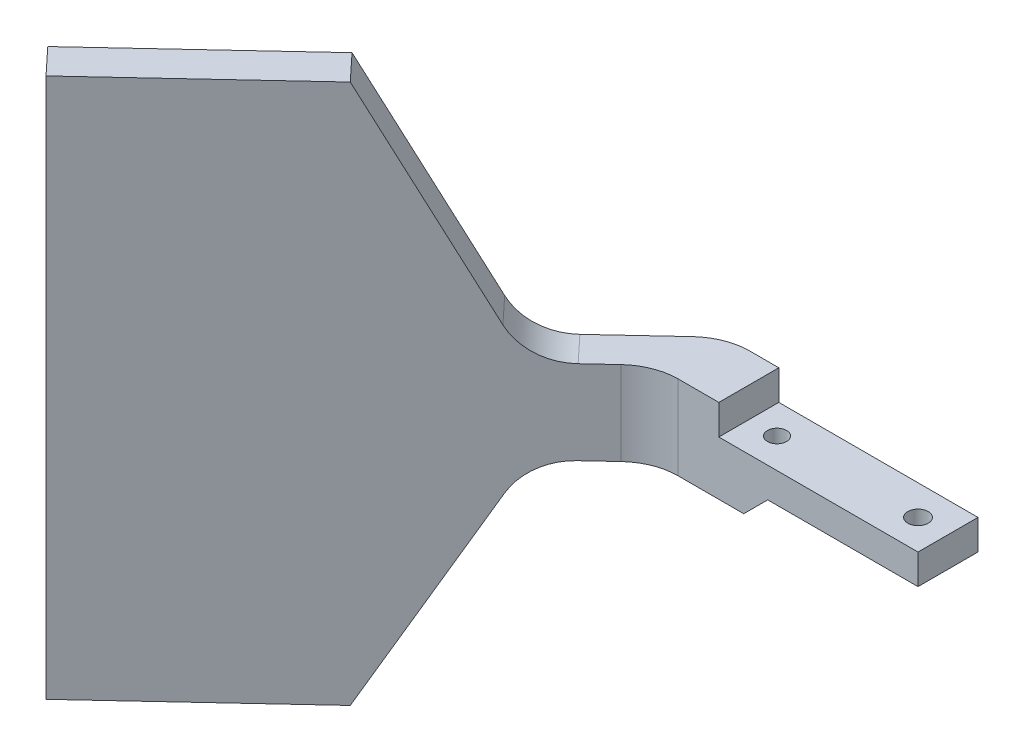
SolidWorks part; units mm, degrees
ref_plane "Front" through (0, 0, 0) normal (0, 0, 1) x (1, 0, 0)
ref_plane "Top" through (0, 0, 0) normal (0, 1, 0) x (1, 0, 0)
ref_plane "Right" through (0, 0, 0) normal (1, 0, 0) x (0, 0, -1)
sketch "Sketch1" plane through (0, 0, 0) normal (0, 1, 0) x (1, 0, 0)
  line L0 (0, 10) -> (0, 0)
  line L1 (0, 0) -> (42, 0)
  line L3 (0, 10) -> (42, 10)
  line L4 (42, 0) -> (42, 10)
  line L9 (0, 10) -> (-58.5083, -44.5599)
  line L10 (-58.5083, -44.5599) -> (-54.4163, -48.948)
  line L11 (0, 10) -> (4.092, 5.6119)
  line L12 (-54.4163, -48.948) -> (4.092, 5.6119)
  line L13 (0, 0) -> (-1.926, 0)
  line L14 (-1.926, 0) -> (0, 1.796)
  line L15 (0, 1.796) -> (0, 0)
  dimension "D1" = 10
  dimension "D2" = 42
  dimension "D3" = 223
  dimension "D4" = 80
  dimension "D5" = 6
  dimension "D6" = 270
extrude "Boss-Extrude1" add sketch "Sketch1" along normal blind 5 contours L10 L12 L1 L0 L9 | L1 L12 L11 L0 | L12 L1 L4 L3 L11 | L13 L0 L12 region at (1.364, 0, -5.8026) region at (-28.2435, 0, 20.3899) region at (21.8174, 0, -4.9666) region at (-0.642, 0, -0.5987)
sketch "Sketch3" plane through (0, 5, 0) normal (0, 1, 0) x (1, 0, 0)
  line L0 (-58.5083, -44.5599) -> (-54.4163, -48.948)
  line L1 (-54.4163, -48.948) -> (-28.1712, -24.474)
  line L2 (-54.4163, -48.948) -> (-1.926, 0) construction
  line L3 (-28.1712, -24.474) -> (-32.2631, -20.0859)
  line L4 (0, 10) -> (-58.5083, -44.5599) construction
  line L5 (-32.2631, -20.0859) -> (-58.5083, -44.5599)
extrude "Boss-Extrude2" add sketch "Sketch3" along normal blind 45
sketch "Sketch4" plane through (0, 0, 0) normal (0, -1, 0) x (1, 0, 0)
  line L0 (-58.5083, 44.5599) -> (-54.4163, 48.948)
  line L1 (-54.4163, 48.948) -> (-28.1712, 24.474)
  line L2 (-54.4163, 48.948) -> (-1.926, 0) construction
  line L3 (-28.1712, 24.474) -> (-32.2631, 20.0859)
  line L4 (0, -10) -> (-58.5083, 44.5599) construction
  line L5 (-32.2631, 20.0859) -> (-58.5083, 44.5599)
extrude "Boss-Extrude3" add sketch "Sketch4" along normal blind 40
sketch "Sketch5" plane through (-4.9878, 0, -5.3488) normal (-0.682, 0, -0.7314) x (-0.7314, 0, 0.682)
  line L0 (37.2943, -40) -> (37.2943, 0)
  line L1 (37.2943, 0) -> (13.889, 0)
  line L2 (-6.82, 0) -> (37.2943, 0) construction
  line L3 (13.889, 0) -> (37.2943, -40)
  line L4 (13.889, 5) -> (37.2943, 50)
  line L5 (-6.82, 5) -> (37.2943, 5) construction
  line L6 (37.2943, 50) -> (37.2943, 5)
  line L7 (37.2943, 5) -> (13.889, 5)
extrude "Boss-Extrude4" add sketch "Sketch5" against normal blind 6
sketch "Sketch8" plane through (0, 0, 0) normal (0, -1, 0) x (1, 0, 0)
  line L0 (0, -10) -> (-23.7044, 12.1047)
  line L1 (-32.2631, 20.0859) -> (-15.1456, 4.1235) construction
  line L6 (-23.7044, 12.1047) -> (-19.6124, 16.4928)
  line L7 (-28.1712, 24.474) -> (-11.0536, 8.5116) construction
  line L8 (-19.6124, 16.4928) -> (8.7977, -10)
  line L9 (0, -10) -> (42, -10) construction
  line L10 (8.7977, -10) -> (0, -10)
extrude "Boss-Extrude6" add sketch "Sketch8" along normal blind 4
sketch "Sketch9" plane through (0, 5, 0) normal (0, 1, 0) x (1, 0, 0)
  line L3 (-16.8573, -5.7197) -> (-32.2631, -20.0859) construction
  line L4 (-24.5602, -12.9028) -> (0, 10)
  line L6 (-24.5602, -12.9028) -> (-16.7996, -13.8699)
  line L7 (-28.1712, -24.474) -> (-11.0536, -8.5116) construction
  line L9 (-16.7996, -13.8699) -> (8.7977, 10)
  line L10 (0, 10) -> (42, 10) construction
  line L11 (8.7977, 10) -> (0, 10)
  line L12 (42, 0) -> (-1.926, 0) construction
  line L13 (8.7977, 0) -> (-1.926, 0)
  line L14 (-1.926, 0) -> (8.7977, 10)
  line L15 (8.7977, 10) -> (17.9505, 10)
  line L16 (17.9505, 10) -> (17.9505, 0)
  line L17 (17.9505, 0) -> (8.7977, 0)
  line M3 (-1.926, 0) -> (42, 0)
  line M6 (42, 10) -> (0, 10)
sketch "Sketch10" plane through (0, 5, 0) normal (0, 1, 0) x (1, 0, 0)
  line L0 (8.7977, 10) -> (8.7977, 0)
  line L1 (8.7977, 0) -> (-1.926, 0)
  line L2 (-1.926, 0) -> (-16.7996, -13.8699)
  line L3 (-16.7996, -13.8699) -> (-20.8916, -9.4817)
  line L4 (-20.8916, -9.4817) -> (0, 10)
  line L5 (0, 10) -> (8.7977, 10)
extrude "Boss-Extrude7" add sketch "Sketch10" along normal blind 5
extrude "Boss-Extrude8" add sketch "Sketch9" against normal blind 9 contours L16 L9 M6 M3 region at (10.3631, 5, -4.3843)
chamfer "Chamfer1" distance 5 angle 45 1 edges at (17.9505, -4, -5)
sketch "Sketch11" plane through (0, 5, 0) normal (0, 1, 0) x (1, 0, 0)
  circle A0 centre (13.5, 5) radius 1.6
extrude "Cut-Extrude2" cut sketch "Sketch11" against normal blind 10
fillet "Fillet3" radius 10 4 edges at (0, 3, -10) (-14.8113, -4, 7.9138) (-15.0015, 10, 8.0911) (-1.926, 3, 0)
sketch "Sketch12" plane through (0, 0, 0) normal (0, -1, 0) x (-1, 0, 0)
  circle A0 centre (-37, 5) radius 1.7
extrude "Cut-Extrude3" cut sketch "Sketch12" against normal blind 10
